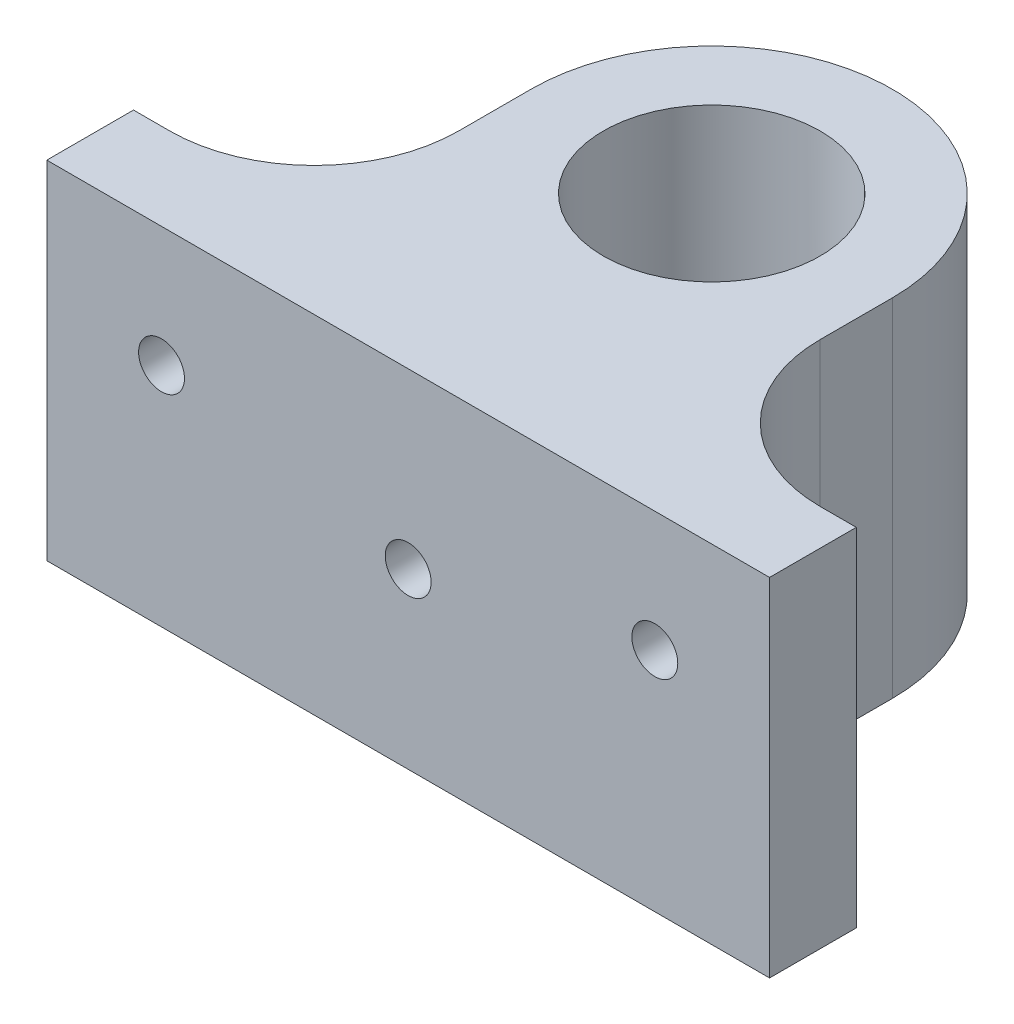
SolidWorks part; units mm, degrees
ref_plane "Front Plane" through (0, 0, 0) normal (0, 0, 1) x (1, 0, 0)
ref_plane "Top Plane" through (0, 0, 0) normal (0, 1, 0) x (1, 0, 0)
ref_plane "Right Plane" through (0, 0, 0) normal (1, 0, 0) x (0, 0, -1)
sketch "Profile-Sketch1" plane through (0, 0, 0) normal (0, 1, 0) x (1, 0, 0)
  line L0 (-25, -21) -> (25, -21)
  line L1 (25, -21) -> (25, -15)
  line L2 (-25, -21) -> (-25, -15)
  line L3 (-25, -15) -> (-22.5, -15)
  line L4 (-12.5, -5) -> (-12.5, 0)
  line L5 (25, -15) -> (22.5, -15)
  line L6 (12.5, -5) -> (12.5, 0)
  circle A0 centre (0, 0) radius 7.5
  arc A6 (12.5, 0) -> (-12.5, 0) centre (0, 0) ccw
  arc A7 (22.5, -15) -> (12.5, -5) centre (22.5, -5) cw
  arc A8 (-12.5, -5) -> (-22.5, -15) centre (-22.5, -5) cw
  dimension "D1" = 15
  dimension "D2" = 12.5
  dimension "D7" = 10
  dimension "D3" = 50
  dimension "D4" = 25
  dimension "D5" = 21
  dimension "D6" = 6
extrude "Profile-Boss-Extrude2" add sketch "Profile-Sketch1" along normal blind 24
sketch "FasteningHoleSketch3" plane through (0, 0, 21) normal (0, 0, 1) x (1, 0, 0)
  line L0 (25, 24) -> (25, 0) construction
  line L1 (-25, 24) -> (-25, 0) construction
  line L2 (-25, 0) -> (25, 0) construction
  circle A2 centre (-17.0625, 15.6776) radius 1.5875
  circle A3 centre (17.0625, 15.6776) radius 1.5875
  dimension "D3" = 3.175
  dimension "D6" = 7.9375
  dimension "D2" = 15.6776
  dimension "D1" = 7.9375
extrude "FasteningHoleCut-Extrude8" cut sketch "FasteningHoleSketch3" against normal through all
sketch "LM8UUFasteningHoleSketch5" plane through (0, 0, 21) normal (0, 0, 1) x (1, 0, 0)
  line L0 (25, 24) -> (25, 0) construction
  line L1 (-25, 0) -> (25, 0) construction
  circle A0 centre (0, 12) radius 1.5875
  circle A1 centre (-17.0625, 15.6776) radius 1.5875 construction
  dimension "D1" = 25
  dimension "D2" = 12
extrude "LM8UUFasteningHoleCut-Extrude9" cut sketch "LM8UUFasteningHoleSketch5" against normal through all
equation "\"RailThickness\"= .125in'Spec"
equation "\"LM8UUDiameter\"= 15mm"
equation "\"MidLeftOrRightSideRailHeight\"= 2.0in"
equation "\"RodStabilizerLength\"= 50mm"
equation "\"HoleOffsetFromEdge\"= \"RailThickness\" * 2.5"
equation "\"StepperMountingHoleOffsetFromItsSide\"= 5.5mm'Spec"
equation "\"StepperMountingHoleOffsetFromLeftOrRightSide\"= \"StepperMountingHoleOffsetFromItsSide\" + \"RailThickness\""
equation "\"StepperMountingHoleDistance\"= 31mm'Spec"
equation "\"LM8UUHeight\"= 24mm'Spec"
equation "\"ZAxisLeadScrewLength\"= 200mm"
equation "\"LegHeight\"= 70mm'Space needed for PSU/Stepper/Electronics"
equation "\"V1 BottomOfLowerRail\"= \"LegHeight\""
equation "\"StepperShaftLength\"= 24mm'Pulley will be attached to the end"
equation "\"V2 ToBedAtTopOfZAxis\"= \"V1 BottomOfLowerRail\" - \"LowerEnclosureThickness\" + \"StepperShaftLength\" + \"ZAxisLeadScrewLength\" - \"LM8UUHeight\" / 2"
equation "\"HotEndToTopOfXAxisGB\"= 63.315144mm'Measured from the100.Should be 63.315144"
equation "\"TopOfGBToBottomOfLinearRail\"= \"LinearGBWidth\" / 2 + \"LinearRailWidth\" / 2"
equation "\"LinearGBWidth\"= 27mm'Spec"
equation "\"V5 ToBottomOfXAxisLinearRail\"= \"V4 ToTopOfBuildPlate/HotEndTip\" + \"HotEndToTopOfXAxisGB\" - \"TopOfGBToBottomOfLinearRail\""
equation "\"LinearRailWidth\"= 12mm'Spec"
equation "\"V6 ToBottomOfGantryPulley\"= \"V5 ToBottomOfXAxisLinearRail\" - \"DistanceFromGABTopToLowerPulley\""
equation "\"GABUpperHeight\"= 6mm"
equation "\"GABMidWallHeight\"= 28mm'Must equal 28 or changes alignment"
equation "\"20TGT2PulleyWidth\"= 8.7mm'The STL of the Pulley in the diagram is a bit larger"
equation "\"GABMidShortRiserHeight\"= \"GABMidWallHeight\" / 2 - \"20TGT2PulleyWidth\"'Equals 5.3"
equation "\"GABRiserBossOffset\"= 0.8mm'Aligns Pulleys"
equation "\"DistanceFromGABTopToLowerPulley\"= \"GABUpperHeight\" + \"GABMidWallHeight\" - \"GABMidShortRiserHeight\" + \"GABRiserBossOffset\" / 2"
equation "\"V7 ToTopOfMidBackRail\"= \"V6 ToBottomOfGantryPulley\" + \"StepperShaftLength\""
equation "\"BedToBuildPlateStandoffLength\"= 15mm"
equation "\"BuildPlateHeight\"= 8mm'Spec"
equation "\"V4 ToTopOfBuildPlate/HotEndTip\"= \"V2 ToBedAtTopOfZAxis\" + \"BedToBuildPlateStandoffLength\" + \"BuildPlateHeight\""
equation "\"FasteningHoleDiameter\"= .125in"
equation "\"RodStabilizerHeight\"= \"LM8UUHeight\""
equation "\"LowerEnclosureThickness\"= 5mm"
equation "\"D1@Profile-Sketch1\" = \"LM8UUDiameter\""
equation "\"D3@Profile-Sketch1\" = \"RodStabilizerLength\""
equation "\"D4@Profile-Sketch1\" = \"RodStabilizerLength\" / 2"
equation "\"RodStabilizerWidthFromMidRailToZAxisRodCenter\"= \"StepperMountingHoleOffsetFromLeftOrRightSide\" + \"StepperMountingHoleDistance\" / 2 - \"RailThickness\""
equation "\"StandardWallThickness\"= 3mm"
equation "\"D6@Profile-Sketch1\" = \"StandardWallThickness\" * 2"
equation "\"D1@Profile-Boss-Extrude2\"= \"RodStabilizerHeight\""
equation "\"D6@FasteningHoleSketch3\"=\"HoleOffsetFromEdge\""
equation "\"D2@LM8UUFasteningHoleSketch5\"=\"LM8UUHeight\"/2"
equation "\"V8 ToTopOfMidSideRail\"= \"V7 ToTopOfMidBackRail\" - \"RailThickness\""
equation "\"D5@Profile-Sketch1\"=\"RodStabilizerWidthFromMidRailToZAxisRodCenter\""
equation "\"V3 ToTopOfZAxisLM8UU\"= \"V2 ToBedAtTopOfZAxis\" + \"LM8UUHeight\""
equation "\"RodStabilizerMountingHoleYOffsetFromBottom\"= \"RodStabilizerHeight\" - ( \"V3 ToTopOfZAxisLM8UU\" - \"V8 ToTopOfMidSideRail\" + \"MidLeftOrRightSideRailHeight\" ) + \"HoleOffsetFromEdge\""
equation "\"D2@FasteningHoleSketch3\"=\"RodStabilizerMountingHoleYOffsetFromBottom\""
equation "\"D3@FasteningHoleSketch3\"=\"FasteningHoleDiameter\""
